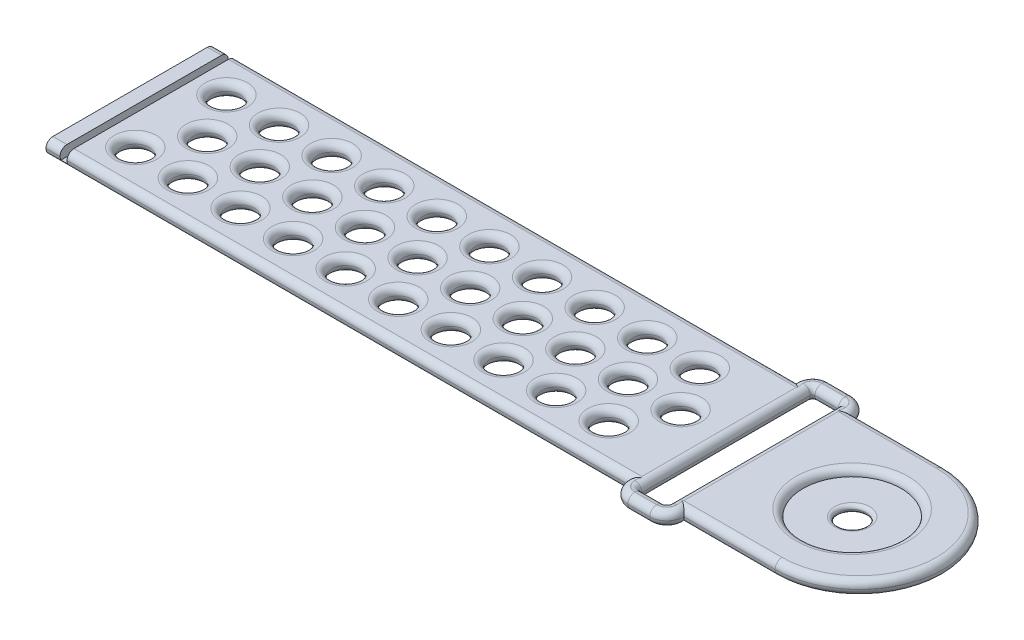
SolidWorks part; units mm, degrees
ref_plane "Front Plane" through (0, 0, 0) normal (0, 0, 1) x (1, 0, 0)
ref_plane "Top Plane" through (0, 0, 0) normal (0, 1, 0) x (1, 0, 0)
ref_plane "Right Plane" through (0, 0, 0) normal (1, 0, 0) x (0, 0, -1)
sketch "Sketch1" plane through (0, 0, 0) normal (0, 1, 0) x (1, 0, 0)
  line L1 (-40.0551, 33.7559) -> (43.9449, 33.7559)
  line L2 (-40.0551, 33.7559) -> (-40.0551, 9.7559)
  line L3 (-40.0551, 9.7559) -> (43.9449, 9.7559)
  line L7 (47.9451, 33.7559) -> (47.9451, 9.7559) construction
  line L8 (51.9454, 33.7559) -> (51.9454, 9.7559) construction
  line L9 (43.9449, 33.7559) -> (43.9449, 9.7559) construction
  line L10 (47.905, 33.7559) -> (49.4992, 33.7559) construction
  line L11 (51.9454, 33.7559) -> (64.9454, 33.7559)
  line L12 (46.3108, 33.7559) -> (47.905, 33.7559) construction
  line L13 (46.3108, 9.7559) -> (47.9451, 9.7559) construction
  line L14 (51.9454, 9.7559) -> (64.9454, 9.7559)
  line L15 (47.9451, 9.7559) -> (49.9451, 9.7559) construction
  line L16 (43.9449, 33.7559) -> (46.3108, 33.7559) construction
  line L17 (49.4992, 33.7559) -> (51.9454, 33.7559) construction
  line L18 (49.9451, 9.7559) -> (51.9454, 9.7559) construction
  line L19 (43.9449, 9.7559) -> (46.3108, 9.7559) construction
  line L20 (46.2854, 36.0965) -> (49.6048, 36.0965)
  line L21 (49.5051, 7.3157) -> (46.3851, 7.3157)
  line L22 (46.2854, 34.0965) -> (49.6048, 34.0965)
  line L23 (49.5051, 9.3157) -> (46.3851, 9.3157)
  line L24 (45.9449, 33.7559) -> (45.9449, 9.7559)
  line L25 (49.9454, 33.7559) -> (49.9454, 9.7559)
  arc A6 (64.9454, 9.7559) -> (64.9454, 33.7559) centre (64.9454, 21.7559) ccw
  arc A7 (64.9454, 33.7559) -> (64.9454, 9.7559) centre (64.9454, 21.7559) ccw construction
  arc A8 (43.9449, 9.7559) -> (46.3851, 7.3157) centre (46.3851, 9.7559) ccw
  arc A9 (49.5051, 7.3157) -> (51.9454, 9.7559) centre (49.5051, 9.7559) ccw
  arc A10 (51.9454, 33.7559) -> (49.6048, 36.0965) centre (49.6048, 33.7559) ccw
  arc A11 (46.2854, 36.0965) -> (43.9449, 33.7559) centre (46.2854, 33.7559) ccw
  arc A12 (49.9454, 33.7559) -> (49.6048, 34.0965) centre (49.6048, 33.7559) ccw
  arc A13 (46.2854, 34.0965) -> (45.9449, 33.7559) centre (46.2854, 33.7559) ccw
  arc A14 (45.9449, 9.7559) -> (46.3851, 9.3157) centre (46.3851, 9.7559) ccw
  arc A15 (49.5051, 9.3157) -> (49.9454, 9.7559) centre (49.5051, 9.7559) ccw
  point P6 (47.905, 21.7584)
  point P11 (47.905, 21.7584)
  dimension "D1" = 2
  dimension "D2" = 13
  dimension "D4" = 12
  dimension "D3" = 24
  dimension "D5" = 84
extrude "Boss-Extrude1" add sketch "Sketch1" along normal blind 2
fillet "Fillet1" radius 0.99 40 edges at (49.8456, 0, -33.9967) (49.8456, 2, -33.9967) (49.9454, 0, -21.7559) (49.8164, 0, -9.4446) (47.9451, 0, -9.3157) (46.0738, 0, -9.4446) (45.9449, 0, -21.7559) (46.0446, 0, -33.9967) (47.9451, 0, -34.0965) (1.9449, 0, -9.7559) (44.6596, 0, -8.0304) (47.9451, 0, -7.3157) (51.2306, 0, -8.0304) (58.4454, 0, -9.7559) (76.9454, 0, -21.7559) (58.4454, 0, -33.7559) (51.2598, 0, -35.4109) (47.9451, 0, -36.0965) (44.6304, 0, -35.4109) (1.9449, 0, -33.7559) (-40.0551, 0, -21.7559) (46.0446, 2, -33.9967) (45.9449, 2, -21.7559) (46.0738, 2, -9.4446) (47.9451, 2, -9.3157) (49.8164, 2, -9.4446) (49.9454, 2, -21.7559) (47.9451, 2, -34.0965) (1.9449, 2, -33.7559) (44.6304, 2, -35.4109) (47.9451, 2, -36.0965) (51.2598, 2, -35.4109) (58.4454, 2, -33.7559) (76.9454, 2, -21.7559) (58.4454, 2, -9.7559) (51.2306, 2, -8.0304) (47.9451, 2, -7.3157) (44.6596, 2, -8.0304) (1.9449, 2, -9.7559) (-40.0551, 2, -21.7559)
sketch "Sketch4" plane through (0, 2, 0) normal (0, 1, 0) x (1, 0, 0)
  line L0 (-31.8179, 28.2559) -> (-28.0651, 21.7559) construction
  line L1 (-28.0651, 21.7559) -> (-31.8179, 15.2559) construction
  line L2 (-39.0651, 32.7659) -> (-39.0651, 10.7459) construction
  line L3 (50.9354, 32.7659) -> (50.9354, 10.7459) construction
  line L5 (44.9549, 10.7459) -> (44.9549, 32.7659) construction
  circle A0 centre (-28.0651, 21.7559) radius 2
  circle A1 centre (-31.8179, 28.2559) radius 2
  circle A2 centre (-31.8179, 15.2559) radius 2
  circle A3 centre (-24.3151, 28.2559) radius 2
  circle A4 centre (-20.5624, 21.7559) radius 2
  circle A5 centre (-24.3151, 15.2559) radius 2
  circle A6 centre (-16.8124, 28.2559) radius 2
  circle A7 centre (-13.0596, 21.7559) radius 2
  circle A8 centre (-16.8124, 15.2559) radius 2
  circle A9 centre (-9.3096, 28.2559) radius 2
  circle A10 centre (-5.5568, 21.7559) radius 2
  circle A11 centre (-9.3096, 15.2559) radius 2
  circle A12 centre (-1.8068, 28.2559) radius 2
  circle A13 centre (1.946, 21.7559) radius 2
  circle A14 centre (-1.8068, 15.2559) radius 2
  circle A15 centre (5.696, 28.2559) radius 2
  circle A16 centre (9.4487, 21.7559) radius 2
  circle A17 centre (5.696, 15.2559) radius 2
  circle A18 centre (13.1987, 28.2559) radius 2
  circle A19 centre (16.9515, 21.7559) radius 2
  circle A20 centre (13.1987, 15.2559) radius 2
  circle A21 centre (63.9354, 21.7559) radius 2
  circle A22 centre (20.7015, 28.2559) radius 2
  circle A23 centre (24.4543, 21.7559) radius 2
  circle A24 centre (20.7015, 15.2559) radius 2
  circle A25 centre (28.2043, 28.2559) radius 2
  circle A26 centre (31.9571, 21.7559) radius 2
  circle A27 centre (28.2043, 15.2559) radius 2
  circle A28 centre (35.7071, 28.2559) radius 2
  circle A29 centre (39.4598, 21.7559) radius 2
  circle A30 centre (35.7071, 15.2559) radius 2
  point P4 (50.9354, 21.7559)
  point P12 (0, 0)
  point P73 (44.9549, 21.7559)
  point P74 (35.7071, 28.2559)
  dimension "D7" = 4
  dimension "D8" = 4
  dimension "D1" = 120
  dimension "D2" = 13
  dimension "D3" = 11
  dimension "D5" = 3.75
  dimension "D6" = 13
  dimension "D4" = 10
extrude "Cut-Extrude2" cut sketch "Sketch4" against normal through all
sketch "Sketch5" plane through (0, 2, 0) normal (0, 1, 0) x (1, 0, 0)
  circle A0 centre (63.9354, 21.7559) radius 7
  circle A2 centre (63.9354, 21.7559) radius 2 construction
  dimension "D1" = 14
extrude "Cut-Extrude3" cut sketch "Sketch5" against normal blind 1
fillet "Fillet3" radius 1 61 edges at (-28.0651, 0, -19.7559) (5.696, 0, -26.2559) (5.696, 0, -13.2559) (16.9515, 0, -19.7559) (13.1987, 0, -26.2559) (13.1987, 0, -13.2559) (-24.3151, 0, -13.2559) (-13.0596, 0, -19.7559) (-16.8124, 0, -26.2559) (-24.3151, 0, -26.2559) (-20.5624, 0, -19.7559) (-31.8179, 0, -13.2559) (-31.8179, 0, -26.2559) (1.946, 0, -19.7559) (-1.8068, 0, -26.2559) (-1.8068, 0, -13.2559) (9.4487, 0, -19.7559) (-16.8124, 0, -13.2559) (-5.5568, 0, -19.7559) (-9.3096, 0, -26.2559) (-9.3096, 0, -13.2559) (-28.0651, 2, -19.7559) (5.696, 2, -26.2559) (5.696, 2, -13.2559) (16.9515, 2, -19.7559) (13.1987, 2, -26.2559) (13.1987, 2, -13.2559) (-24.3151, 2, -13.2559) (-13.0596, 2, -19.7559) (-16.8124, 2, -26.2559) (-24.3151, 2, -26.2559) (-20.5624, 2, -19.7559) (-31.8179, 2, -13.2559) (-31.8179, 2, -26.2559) (1.946, 2, -19.7559) (-1.8068, 2, -26.2559) (-1.8068, 2, -13.2559) (9.4487, 2, -19.7559) (-16.8124, 2, -13.2559) (-5.5568, 2, -19.7559) (-9.3096, 2, -26.2559) (-9.3096, 2, -13.2559) (24.4543, 0, -19.7559) (20.7015, 0, -26.2559) (20.7015, 0, -13.2559) (35.7071, 0, -13.2559) (35.7071, 0, -26.2559) (31.9571, 0, -19.7559) (28.2043, 0, -26.2559) (28.2043, 0, -13.2559) (39.4598, 0, -19.7559) (24.4543, 2, -19.7559) (20.7015, 2, -26.2559) (20.7015, 2, -13.2559) (35.7071, 2, -13.2559) (35.7071, 2, -26.2559) (31.9571, 2, -19.7559) (28.2043, 2, -26.2559) (28.2043, 2, -13.2559) (39.4598, 2, -19.7559) (63.9354, 2, -14.7559)
fillet "Fillet4" radius 0.5 2 edges at (63.9354, 1, -19.7559) (63.9354, 0, -19.7559)
sketch "Sketch6" plane through (0, 2, 0) normal (0, 1, 0) x (1, 0, 0)
  line L1 (-39.0551, 9.7559) -> (-42.3695, 9.7559)
  line L2 (-39.0551, 9.7559) -> (-39.0551, 33.7559)
  line L3 (-39.0551, 33.7559) -> (-42.3695, 33.7559)
  line L4 (-42.3695, 9.7559) -> (-42.3695, 33.7559)
  line L6 (-40.0551, 33.7559) -> (43.9449, 33.7559) construction
  line L7 (43.9449, 9.7559) -> (-40.0551, 9.7559) construction
extrude "Cut-Extrude4" cut sketch "Sketch6" against normal through all both and the other way through all
sketch "Sketch7" plane through (0, 2, 0) normal (0, 1, 0) x (1, 0, 0)
  line L0 (-39.0551, 33.7559) -> (43.9449, 33.7559) construction
  line L1 (-37.0551, 33.7559) -> (-36.0551, 33.7559)
  line L2 (-37.0551, 33.7559) -> (-37.0551, 9.7559)
  line L3 (-37.0551, 9.7559) -> (-36.0551, 9.7559)
  line L4 (-36.0551, 33.7559) -> (-36.0551, 9.7559)
  line L5 (43.9449, 9.7559) -> (-39.0551, 9.7559) construction
  line L7 (-39.0551, 10.7459) -> (-39.0551, 9.7559) construction
  dimension "D1" = 2
  dimension "D2" = 1
extrude "Cut-Extrude5" cut sketch "Sketch7" against normal blind 1.5 and the other way through all
